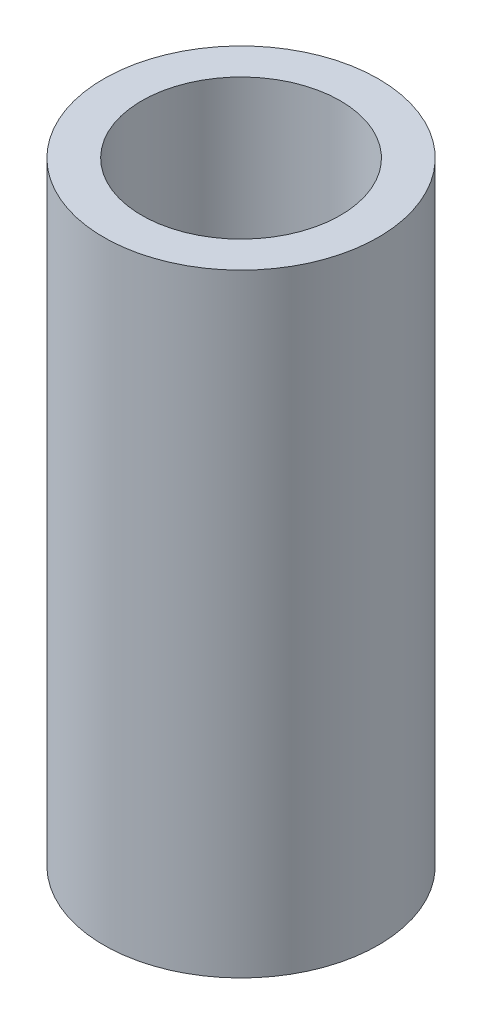
SolidWorks part; units mm, degrees
ref_plane "Front Plane" through (0, 0, 0) normal (0, 0, 1) x (1, 0, 0)
ref_plane "Top Plane" through (0, 0, 0) normal (0, 1, 0) x (1, 0, 0)
ref_plane "Right Plane" through (0, 0, 0) normal (1, 0, 0) x (0, 0, -1)
sketch "Sketch1" plane through (0, 0, 0) normal (0, 0, 1) x (1, 0, 0)
  line L0 (0, 0) -> (0, 31.1949) construction
  line L2 (4.05, 0) -> (5.6, 0)
  line L3 (4.05, 0) -> (4.05, 25)
  line L4 (4.05, 25) -> (5.6, 25)
  line L5 (5.6, 0) -> (5.6, 25)
  point P7 (0, 31.1949)
  dimension "D1" = 8.1
  dimension "D2" = 11.2
  dimension "D3" = 25
revolve "Revolve1" add sketch "Sketch1" angle 360 about L0
